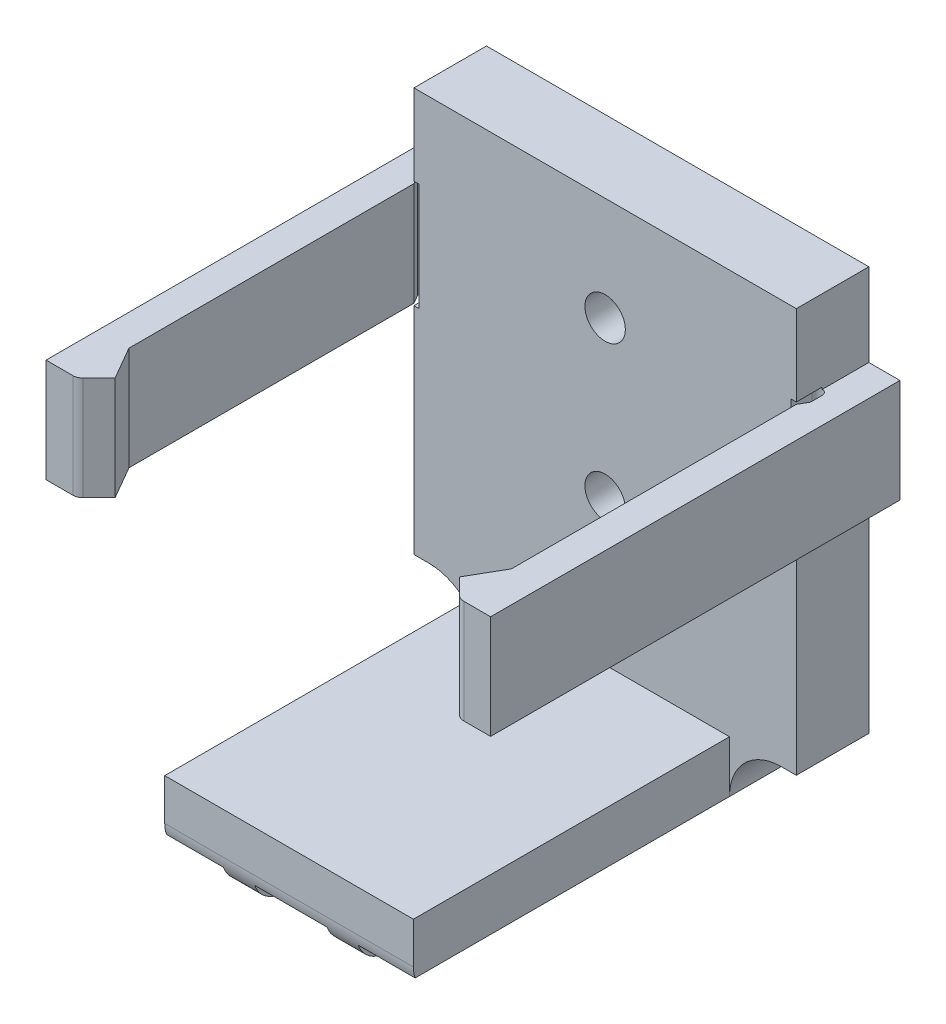
SolidWorks part; units mm, degrees
ref_plane "前基準面" through (0, 0, 0) normal (0, 0, 1) x (1, 0, 0)
ref_plane "上基準面" through (0, 0, 0) normal (0, 1, 0) x (1, 0, 0)
ref_plane "右基準面" through (0, 0, 0) normal (1, 0, 0) x (0, 0, -1)
ref_axis "基準軸1" through (0, -55, 0) along (0, 1, 0)
ref_axis "基準軸2" through (-88.99, 0, 0) along (1, 0, 0)
ref_axis "基準軸3" through (0, 0, 55) along (0, 0, -1)
sketch "草圖1" plane through (0, 0, 0) normal (0, 0, 1) x (1, 0, 0)
  line L1 (0, 0) -> (36.9, 0)
  line L2 (0, 0) -> (0, 39)
  line L3 (0, 39) -> (36.9, 39)
  line L4 (36.9, 0) -> (36.9, 39)
  dimension "D1" = 36.9
  dimension "D2" = 39
extrude "填料-伸長1" add sketch "草圖1" along normal blind 7
ref_plane "平面1" through (18.45, 0, 0) normal (-1, 0, 0) x (0, 0, 1)
sketch "草圖2" plane through (0, 0, 0) normal (0, -1, 0) x (1, 0, 0)
  line L0 (20.295, 0) -> (-20.295, 0) construction
  line L1 (6.45, 37.5) -> (30.45, 37.5)
  line L2 (6.45, 37.5) -> (6.45, 0)
  line L3 (6.45, 0) -> (30.45, 0)
  line L4 (30.45, 37.5) -> (30.45, 0)
  line L6 (18.45, 3.85) -> (18.45, -3.85) construction
  point P6 (18.45, 37.5)
  dimension "D1" = 24
  dimension "D2" = 37.5
extrude "填料-伸長2" add sketch "草圖2" along normal blind 5
sketch "草圖4" plane through (36.9, 0, 0) normal (1, 0, 0) x (0, 0, -1)
  line L0 (3.85, 0) -> (-3.85, 0) construction
  line L1 (-39.5, 31) -> (0, 31)
  line L2 (-39.5, 31) -> (-39.5, 21)
  line L3 (-39.5, 21) -> (0, 21)
  line L4 (0, 31) -> (0, 21)
  line L5 (0, 20.295) -> (0, -20.295) construction
  dimension "D1" = 21
  dimension "D2" = 10
  dimension "D3" = 39.5
extrude "填料-伸長3" add sketch "草圖4" along normal blind 3
sketch "草圖5" plane through (0, 31, 0) normal (0, 1, 0) x (1, 0, 0)
  line L0 (36.9, -39.5) -> (35.0699, -37.6699)
  line L2 (36.9, -7) -> (36.9, -39.5) construction
  line L3 (36.9, -39.5) -> (36.9, -34.5)
  line L4 (36.9, -34.5) -> (35.0699, -37.6699)
  dimension "D1" = 30
  dimension "D2" = 45
  dimension "D3" = 5
extrude "填料-伸長4" add sketch "草圖5" against normal up to surface (10 mm away) up to face at (38.1, 21, 17.2)
sketch "草圖6" plane through (0, 31, 0) normal (0, 1, 0) x (1, 0, 0)
  line L0 (-88.99, 0) -> (88.99, 0) construction
  line L1 (36.3981, -7) -> (36.8991, -7)
  line L2 (36.3981, -7) -> (36.3981, -5)
  line L4 (37.4, -6.1323) -> (37.4, -5)
  line L6 (36.9, 0) -> (36.9, -7) construction
  line L7 (36.8991, -7) -> (37.4, -6.1323)
  arc A0 (37.4, -5) -> (36.3981, -5) centre (36.8991, -5) ccw
  dimension "D1" = 0.5009
  dimension "D2" = 2
  dimension "D3" = 1.0019
  dimension "D4" = 5
  dimension "D5" = 0.5
  dimension "D6" = 0.5009
  dimension "D7" = 120
  dimension "D8" = 1.1323
extrude "除料-伸長3" cut sketch "草圖6" against normal up to surface (10 mm away) up to face at (37.4957, 21, 22.5957)
extrude "除料-伸長4" cut sketch "草圖6<2>" along normal blind 0.2
sketch "草圖6<2>" plane through (0, 31, 0) normal (0, 1, 0) x (1, 0, 0) same geometry as "草圖6"
extrude "除料-伸長5" cut sketch "草圖6<3>" against normal blind 0.2 from surface starting at face at (37.3794, 21, 16.4269)
sketch "草圖6<3>" plane through (0, 31, 0) normal (0, 1, 0) x (1, 0, 0) same geometry as "草圖6"
fillet "圓角1" radius 5 2 edges at (6.45, 0, 3.5) (30.45, 0, 3.5)
fillet "圓角2" radius 1 1 edges at (36.9, 26, 39.5)
mirror "鏡射4" about plane through (18.45, 0, 0) normal (-1, 0, 0) of "除料-伸長5", "除料-伸長4", "除料-伸長3", "填料-伸長4", "填料-伸長3", "填料-伸長2"
fillet "圓角3" radius 1 1 edges at (0, 26, 39.5)
sketch "草圖7" plane through (0, -5, 0) normal (0, -1, 0) x (1, 0, 0)
  line L0 (23.595, 0) -> (-23.595, 0) construction
  line L1 (11.95, 0) -> (14.95, 0)
  line L2 (11.95, 0) -> (11.95, 37.5)
  line L3 (11.95, 37.5) -> (14.95, 37.5)
  line L4 (14.95, 0) -> (14.95, 37.5)
  line L5 (30.45, 37.5) -> (6.45, 37.5) construction
  line L7 (21.95, 0) -> (24.95, 0)
  line L8 (21.95, 0) -> (21.95, 37.5)
  line L9 (21.95, 37.5) -> (24.95, 37.5)
  line L10 (24.95, 0) -> (24.95, 37.5)
  point P12 (13.45, 37.5)
  point P13 (18.45, 37.5)
  point P14 (23.45, 37.5)
  dimension "D1" = 5
  dimension "D2" = 5
  dimension "D3" = 3
  dimension "D4" = 3
extrude "填料-伸長5" add sketch "草圖7" along normal blind 2
fillet "圓角4" radius 3 1 edges at (13.45, -7, 37.5)
sketch "草圖8" plane through (0, 0, 7) normal (0, 0, 1) x (1, 0, 0)
  line L0 (18.45, 3.85) -> (18.45, -3.85) construction
  line L1 (36.9, 39) -> (0, 39) construction
  circle A0 centre (18.45, 29) radius 1.95
  circle A1 centre (18.45, 14) radius 1.95
  dimension "D1" = 3.9
  dimension "D2" = 3.9
  dimension "D4" = 15
  dimension "D3" = 10
extrude "除料-伸長6" cut sketch "草圖8" against normal through all
